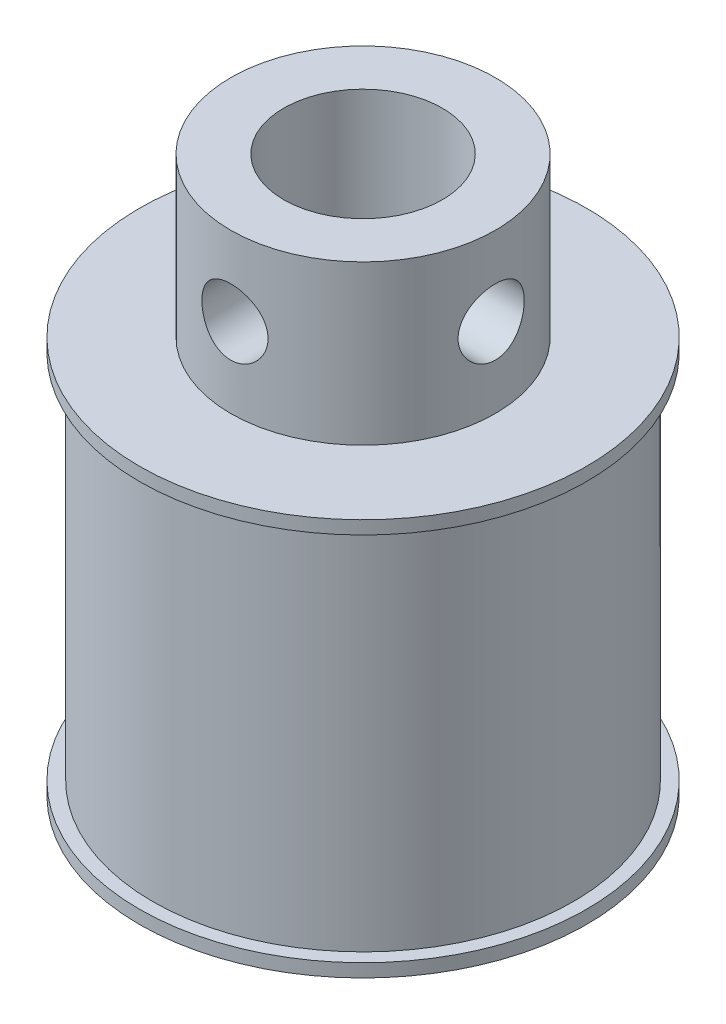
SolidWorks part; units mm, degrees
ref_plane "Alzado" through (0, 0, 0) normal (1, 0, 0) x (0, 1, 0)
ref_plane "Planta" through (0, 0, 0) normal (0, 0, 1) x (0, 1, 0)
ref_plane "Vista lateral" through (0, 0, 0) normal (0, 1, 0) x (-1, 0, 0)
sketch "Croquis1" plane through (0, 0, 0) normal (0, 1, 0) x (-1, 0, 0)
  circle A0 centre (0, 0) radius 7.95
  dimension "D1" = 15.9
extrude "Saliente-Extruir1" add sketch "Croquis1" along normal mid plane 15
sketch "Croquis2" plane through (0, 7.5, 0) normal (0, 1, 0) x (-1, 0, 0)
  circle A3 centre (0, 0) radius 8.45
  dimension "D1" = 16.9
extrude "Saliente-Extruir2" add sketch "Croquis2" against normal blind 0.5
extrude "Saliente-Extruir3" add sketch "Croquis2<2>" along normal blind 0.5 from surface starting at face at (0, -7.5, 7.95)
sketch "Croquis2<2>" plane through (0, 7.5, 0) normal (0, 1, 0) x (-1, 0, 0) same geometry as "Croquis2"
sketch "Croquis3" plane through (0, -7.5, 0) normal (0, 1, 0) x (-1, 0, 0)
  circle A0 centre (0, 0) radius 5
  dimension "D1" = 10
extrude "Saliente-Extruir4" add sketch "Croquis3" along normal blind 21
sketch "Croquis4" plane through (0, -7, 0) normal (0, 1, 0) x (-1, 0, 0)
  circle A0 centre (0, 0) radius 3
  dimension "D1" = 6
extrude "Cortar-Extruir1" cut sketch "Croquis4" against normal through all both and the other way through all
sketch "Croquis5" plane through (0, 0, 0) normal (0, 0, 1) x (0, 1, 0)
  line L4 (10.5, 5) -> (10.5, -5) construction
  line L5 (13.5, 5) -> (7.5, 5) construction
  line L9 (7.5, -5) -> (7.5, 5) construction
  line L10 (7.5, -5) -> (7.5, 5) construction
  point P10 (10.5, 0)
sketch "Croquis6" plane through (0, 0, 0) normal (1, 0, 0) x (0, 1, 0)
  point P0 (10.5, 0)
hole_wizard "Taladro roscado M32" positions "Croquis6" profile "Croquis7" tap size "M3" standard "DIN" end condition up to next
sketch "Croquis7" plane through (0, 10.5, 0) normal (0, 1, 0) x (0, 0, 1)
  line L0 (0, 0) -> (0, 5)
  line L1 (0, 5) -> (1.25, 5)
  line L2 (1.25, 5) -> (1.25, 0)
  line L5 (1.25, 0) -> (0, 0)
  line L11 (0, -6.35) -> (0, 107.95) construction
  dimension "Diámetro de perforador para roscar hasta el siguiente" = 2.5
  dimension "Profundidad de perforador para roscar hasta el siguiente" = 5
cosmetic thread "Rosca de taladro1" parameters "D2"=3
hole_wizard "Taladro roscado M31" positions "Croquis5" profile "Croquis9" tap size "M3" standard "DIN" end condition through all
sketch "Croquis9" plane through (0, 10.5, 0) normal (1, 0, 0) x (0, 1, 0)
  line L0 (0, 0) -> (0, 8.45)
  line L1 (0, 8.45) -> (1.25, 8.45)
  line L2 (1.25, 8.45) -> (1.25, 0)
  line L5 (1.25, 0) -> (0, 0)
  line L11 (0, -6.35) -> (0, 107.95) construction
  dimension "Diámetro de perforador para roscar hasta el siguiente" = 2.5
  dimension "Profundidad de perforador para roscar hasta el siguiente" = 8.45
cosmetic thread "Rosca de taladro2" parameters "D2"=3
ref_axis "Eje1" through (0, 10.5, 5) along (0, 0, -1)
ref_axis "Eje2" through (5, 10.5, 0) along (-1, 0, 0)
equation "\"Dp\"= 15.9"
equation "\"D1@Croquis1\"=\"Dp\""
equation "\"Dm\"= 10"
equation "\"De\"= \"Dp\" + 1"
equation "\"F\"= 15"
equation "\"L\"= 21"
equation "\"D1@Croquis2\"=\"De\""
equation "\"D1@Saliente-Extruir1\"=\"F\""
equation "\"D1@Saliente-Extruir4\"=\"L\""
equation "\"agujero\"= 6"
equation "\"D1@Croquis4\"=\"agujero\""
